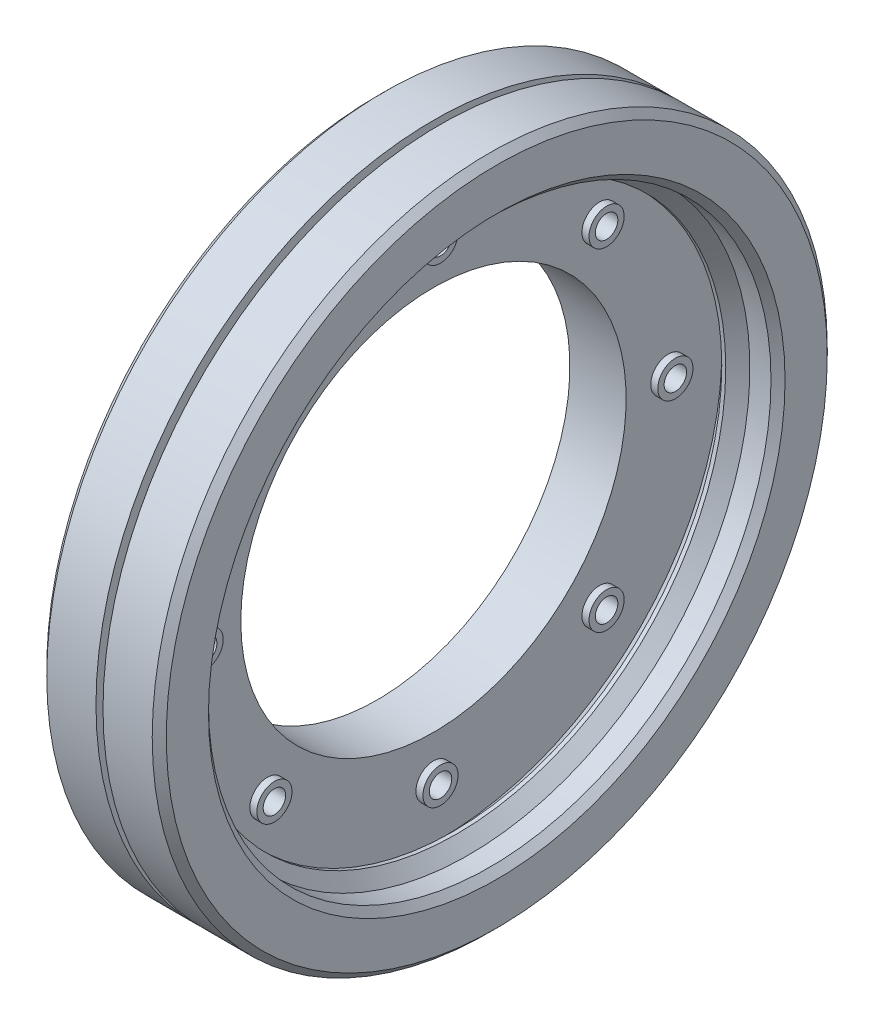
SolidWorks part; units mm, degrees
ref_plane "Front Plane" through (0, 0, 0) normal (0, 0, 1) x (1, 0, 0)
ref_plane "Top Plane" through (0, 0, 0) normal (0, 1, 0) x (1, 0, 0)
ref_plane "Right Plane" through (0, 0, 0) normal (1, 0, 0) x (0, 0, -1)
sketch "Sketch1" plane through (0, 0, 0) normal (0, 1, 0) x (1, 0, 0)
  line L0 (0, 40) -> (2, 38)
  line L1 (0, 48) -> (8, 48)
  line L2 (0, 48) -> (0, 40)
  line L3 (0, 40) -> (8, 40)
  line L4 (8, 48) -> (8, 40)
  line L5 (2, 38) -> (4, 40)
  line L6 (2, 33.4) -> (2, 38) construction
  line L7 (0, 27.4) -> (4, 27.4) construction
  line L8 (0, 27.4) -> (0, 39.4) construction
  line L9 (0, 39.4) -> (4, 39.4) construction
  line L10 (4, 27.4) -> (4, 39.4) construction
  line L11 (0, 27.4) -> (4, 39.4) construction
  line L12 (0, 39.4) -> (4, 27.4) construction
  line L13 (0, 0) -> (5.7592, 0)
  line L15 (-1, 48) -> (-9, 48)
  line L16 (-1, 48) -> (-1, 27.4)
  line L17 (-1, 27.4) -> (-9, 27.4)
  line L18 (-9, 48) -> (-9, 27.4)
  point P9 (2, 33.4)
  dimension "D1" = 40
  dimension "D2" = 45
  dimension "D3" = 4
  dimension "D4" = 8
  dimension "D5" = 8
  dimension "D6" = 12
  dimension "D7" = 4
  dimension "D8" = 1.4
  dimension "D9" = 1
  dimension "D10" = 8
revolve "Revolve1" add sketch "Sketch1" angle 360 about L13 region at (2, 0, -39.3333) region at (4, 0, -44)
revolve "Revolve2" add sketch "Sketch1<4>" angle 360 about L13 region at (-5, 0, -37.7)
sketch "Sketch1<4>" plane through (0, 0, 0) normal (0, 1, 0) x (1, 0, 0) same geometry as "Sketch1"
sketch "Sketch2" plane through (-1, 0, 0) normal (1, 0, 0) x (0, 0, -1)
  circle A0 centre (33.4, 0) radius 1.6
  circle A1 centre (33.4, 0) radius 2.5
  point P0 (33.4, 0)
  dimension "D1" = 3.2
  dimension "D2" = 5
extrude "Cut-Extrude1" cut sketch "Sketch2" against normal blind 10 contours A0
extrude "Boss-Extrude1" add sketch "Sketch2<3>" along normal blind 1
sketch "Sketch2<3>" plane through (-1, 0, 0) normal (1, 0, 0) x (0, 0, -1) same geometry as "Sketch2"
pattern_circular "CirPattern4" count 8 over 360 about axis through (0, 0, 0) along (-1, 0, 0) of "Cut-Extrude1", "Boss-Extrude1"
chamfer "Chamfer4" distance 0.4 angle 45 1 edges at (2, 0, 38)
chamfer "Chamfer5" distance 1 angle 45 2 edges at (8, 0, 48) (8, 0, 40)
chamfer "Chamfer6" distance 1 angle 45 1 edges at (-9, 0, 48)
